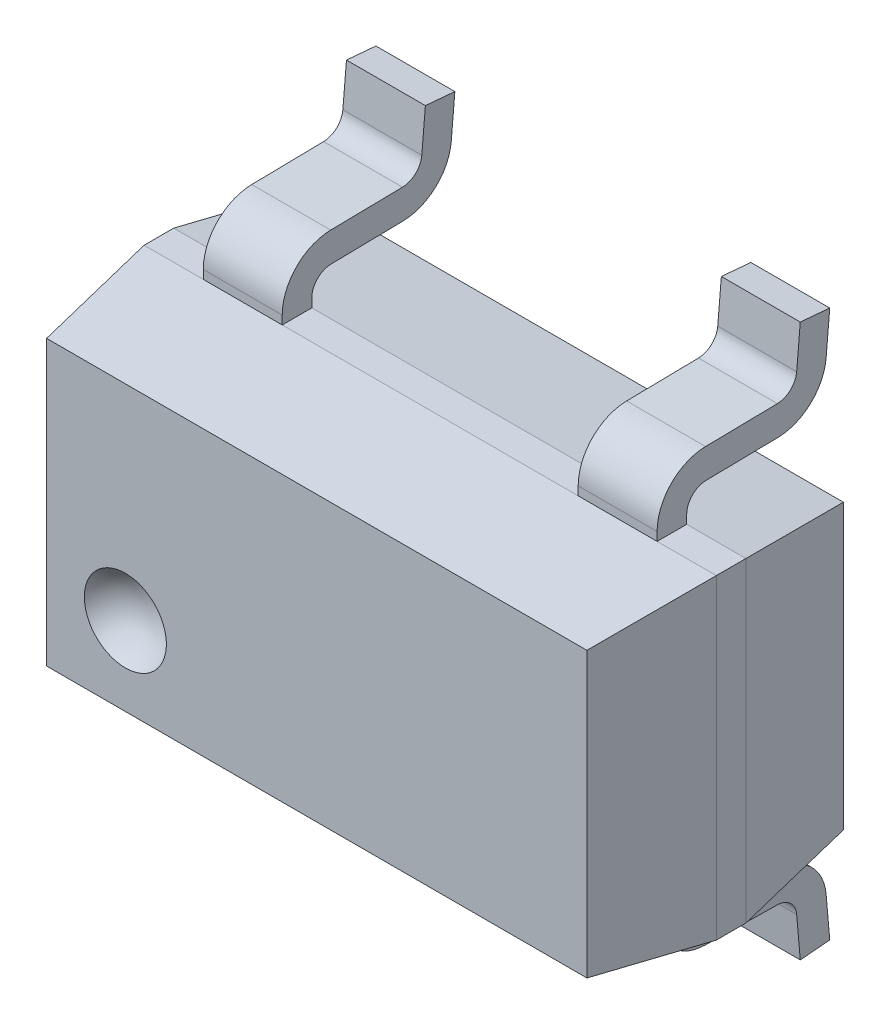
SolidWorks part; units mm, degrees
ref_plane "Top Plane" through (0, 0, 0) normal (0, 0, 1) x (1, 0, 0)
ref_plane "Front Plane" through (0, 0, 0) normal (0, 1, 0) x (1, 0, 0)
ref_plane "Right Plane" through (0, 0, 0) normal (1, 0, 0) x (0, 0, -1)
ref_axis "CenterAxis" through (0, 0, -0.0875) along (0, 0, 1)
ref_plane "Pin1Plane" through (-1.15, 0, 0) normal (1, 0, 0) x (0, 0, -1)
sketch "BodyWxH" plane through (0, 0, 0) normal (1, 0, 0) x (0, 0, -1)
  line L0 (0, 1.54) -> (0, -1.54) construction
  line L1 (-1.45, 0.8) -> (-0.15, 0.8)
  line L2 (-1.45, 0.8) -> (-1.45, -0.8)
  line L3 (-1.45, -0.8) -> (-0.15, -0.8)
  line L4 (-0.15, 0.8) -> (-0.15, -0.8)
  line L6 (-1.45, 0) -> (-0.15, 0) construction
  line L7 (0.0875, 0) -> (-1.8375, 0) construction
  dimension "W" = 1.6
  dimension "SO" = 0.15
  dimension "HMax" = 1.45
extrude "Boss-Body" add sketch "BodyWxH" along normal mid plane 2.9
chamfer "Chamfer1" distance 0.575 angle 8 8 edges at (0, -0.8, 0.15) (1.45, 0, 0.15) (0, 0.8, 0.15) (-1.45, 0, 0.15) (0, 0.8, 1.45) (1.45, 0, 1.45) (0, -0.8, 1.45) (-1.45, 0, 1.45) first distance on face at (0, -0.8, 0.8) first distance on face at (1.45, 0, 0.8) first distance on face at (0, 0.8, 0.8) first distance on face at (-1.45, 0, 0.8)
sketch "LeadCross" plane through (-1.15, 0, 0) normal (1, 0, 0) x (0, 0, -1)
  line L0 (0, -1.3869) -> (-0.1494, -1.4)
  line L1 (-0.1494, -1.4) -> (-0.1677, -1.1912)
  line L2 (-0.2656, -1.1) -> (-0.6294, -1.0936)
  line L3 (-0.875, -0.8437) -> (-0.875, 0.8437)
  line L4 (-0.6294, 1.0936) -> (-0.2656, 1.1)
  line L5 (-0.1677, 1.1912) -> (-0.1494, 1.4)
  line L6 (-0.1494, 1.4) -> (0, 1.3869)
  line L7 (0, 1.3869) -> (-0.0183, 1.1782)
  line L8 (-0.2629, 0.95) -> (-0.6267, 0.9436)
  line L9 (-0.725, 0.8437) -> (-0.725, -0.8437)
  line L10 (-0.6267, -0.9436) -> (-0.2629, -0.95)
  line L11 (-0.0183, -1.1782) -> (0, -1.3869)
  line L12 (0, 1.54) -> (0, -1.54) construction
  line L13 (-0.8, 0) -> (0, 0) construction
  line L14 (0.9625, 0) -> (-0.9625, 0) construction
  line L15 (-0.8, 0.6817) -> (-0.8, -0.6817) construction
  arc A0 (-0.0183, 1.1782) -> (-0.2629, 0.95) centre (-0.2673, 1.2) cw
  arc A1 (-0.2656, 1.1) -> (-0.1677, 1.1912) centre (-0.2673, 1.2) ccw
  arc A2 (-0.2629, -0.95) -> (-0.0183, -1.1782) centre (-0.2673, -1.2) cw
  arc A3 (-0.1677, -1.1912) -> (-0.2656, -1.1) centre (-0.2673, -1.2) ccw
  arc A4 (-0.725, -0.8437) -> (-0.6267, -0.9436) centre (-0.625, -0.8437) ccw
  arc A5 (-0.6294, -1.0936) -> (-0.875, -0.8437) centre (-0.625, -0.8437) cw
  arc A6 (-0.875, 0.8437) -> (-0.6294, 1.0936) centre (-0.625, 0.8437) cw
  arc A7 (-0.6267, 0.9436) -> (-0.725, 0.8437) centre (-0.625, 0.8437) ccw
  dimension "D2" = 5
  dimension "BendRadius" = 0.1
  dimension "LeadThickness" = 0.15
  dimension "ToeLength" = 0.45
  dimension "D4" = 89
  dimension "MidPlane" = 0.8
  dimension "LeadSpan" = 2.8
extrude "Pins" add sketch "LeadCross" along normal blind 0.4
pattern_linear "PatternLeads" count 3 along (1, 0, 0) of "Pins"
ref_plane "Pin1MarkPlane" through (-0.97, 0, 0) normal (1, 0, 0) x (0, 0, -1)
sketch "Pin1Indent" plane through (-0.97, 0, 0) normal (1, 0, 0) x (0, 0, -1)
  line L0 (-1.57, -0.08) -> (-1.57, -0.56) construction
  line L1 (0, 1.54) -> (0, -1.54) construction
  line L2 (-1.57, -0.32) -> (-1.33, -0.32) construction
  line L3 (0.9625, 0) -> (-0.9625, 0) construction
  line L4 (-1.57, -0.08) -> (-1.57, -0.56)
  arc A1 (-1.57, -0.56) -> (-1.57, -0.08) centre (-1.57, -0.32) ccw
  dimension "CutHeight" = 1.57
  dimension "CutSize" = 0.48
  dimension "CutOffset" = 0.32
revolve "Cut-Pin1Indent" cut sketch "Pin1Indent" angle 360 mid plane about L4
other "DeleteFace1" face at (0, 1.0968, 0.4475) face at (-0.2, 1.0446, 0.4442) face at (0, 1.1362, 0.2079) face at (0, 0.9938, 0.7777) face at (0, 0.8218, 0.875) face at (0.2, 1.0446, 0.4442) face at (0, 0.8218, 0.725) face at (0, 0.9037, 0.6861) face at (0, 0.9468, 0.4448) face at (0, 1.0406, 0.1187) face at (0, 1.2825, 0.0091) face at (0, 1.3935, 0.0747) face at (0, 1.2956, 0.1586) and patch yes
equation "\"D1@Chamfer1\" = (\"HMax@BodyWxH\"-\"SO@BodyWxH\"-\"LeadThickness@LeadCross\")/2"
equation "\"D1@Pin1Plane\" = (\"D1@PatternLeads\"-1)*\"LeadPitch@PatternLeads\"/2+(\"LeadWidth@Pins\"/2) ' 1st pin edge plane"
equation "\"CutSize@Pin1Indent\" = \"W@BodyWxH\"*0.3 ' Dent radius is half this value"
equation "\"CutOffset@Pin1Indent\" = \"W@BodyWxH\"/2-(\"W@BodyWxH\"*0.3) ' Dent distance from the center line"
equation "\"D1@Pin1MarkPlane\" = \"D1@Boss-Body\"/2-(\"W@BodyWxH\"*0.3) ' Pin 1 dent lies along this plane"
equation "\"CutHeight@Pin1Indent\" = \"HMax@BodyWxH\"+(\"CutSize@Pin1Indent\"/4) ' Dent is cut by sphere this high"
equation "\"MidPlane@LeadCross\" = (\"HMax@BodyWxH\"+\"SO@BodyWxH\")/2"
